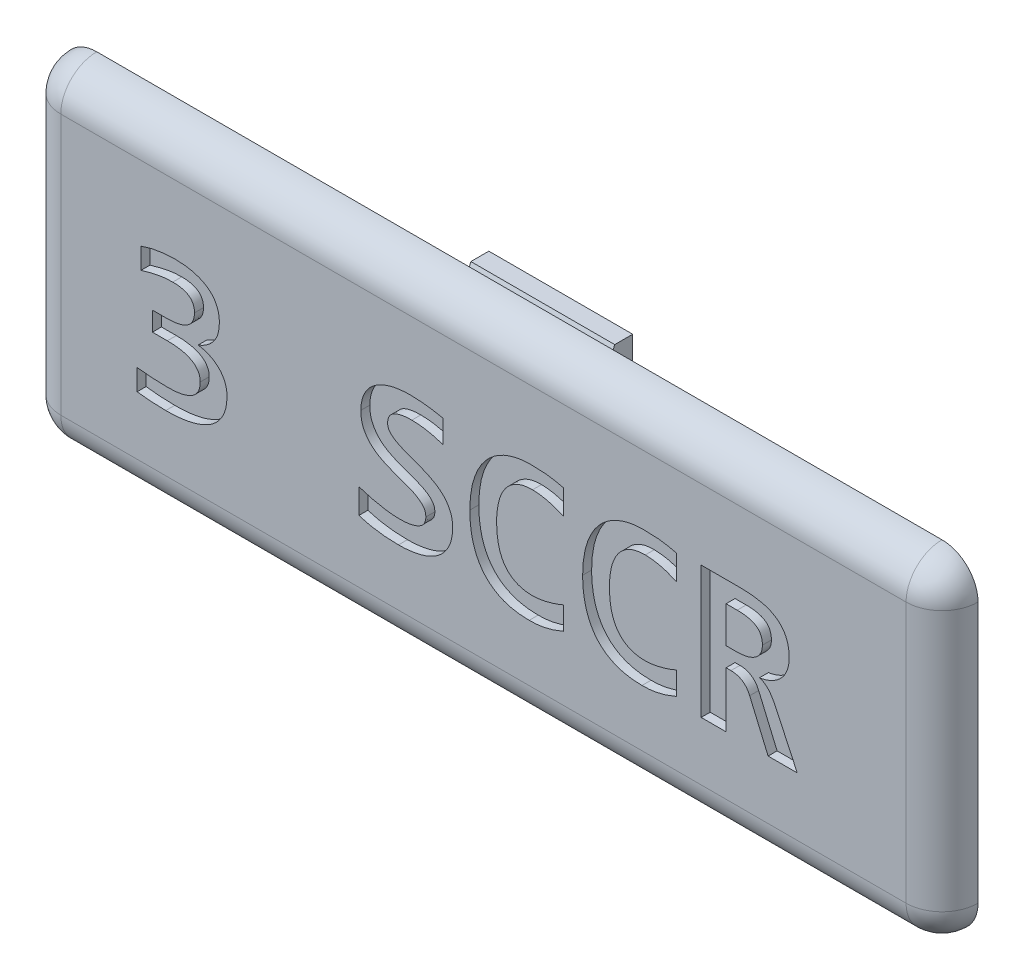
SolidWorks part; units mm, degrees
ref_plane "Front Plane" through (0, 0, 0) normal (0, 0, 1) x (1, 0, 0)
ref_plane "Top Plane" through (0, 0, 0) normal (0, 1, 0) x (1, 0, 0)
ref_plane "Right Plane" through (0, 0, 0) normal (1, 0, 0) x (0, 0, -1)
sketch "Sketch1" plane through (0, 0, 0) normal (0, 0, 1) x (1, 0, 0)
  line L13 (25.5, -7.25) -> (25.5, 7.25) construction
  line L14 (-23.5, -9.25) -> (-5, -9.25) construction
  line L15 (-25.5, 7.25) -> (-25.5, -7.25) construction
  line L16 (13, 9.25) -> (-23.5, 9.25) construction
  line L17 (25.5, -7.25) -> (25.5, 7.25)
  line L18 (-23.5, -9.25) -> (23.5, -9.25)
  line L19 (-25.5, 7.25) -> (-25.5, -7.25)
  line L20 (23.5, 9.25) -> (-23.5, 9.25)
  line L28 (23.75, -7.75) -> (23.75, 7.75)
  line L29 (-23.75, -7.5) -> (11.5, -7.5)
  line L30 (-23.75, 7.5) -> (-23.75, -7.5)
  line L31 (13, 7.5) -> (-23.75, 7.5)
  line L32 (-23.75, -7.5) -> (23.75, -7.5) construction
  line L33 (-23.75, 7.5) -> (-23.75, -7.5) construction
  line L34 (23.75, 7.5) -> (-23.75, 7.5) construction
  line L35 (23.75, -7.75) -> (23.75, 7.75) construction
  arc A0 (25.5, 7.25) -> (23.5, 9.25) centre (23.5, 7.25) ccw construction
  arc A1 (23.5, -9.25) -> (25.5, -7.25) centre (23.5, -7.25) ccw construction
  arc A2 (-25.5, -7.25) -> (-23.5, -9.25) centre (-23.5, -7.25) ccw construction
  arc A3 (-23.5, 9.25) -> (-25.5, 7.25) centre (-23.5, 7.25) ccw construction
  arc A4 (25.5, 7.25) -> (23.5, 9.25) centre (23.5, 7.25) ccw
  arc A5 (23.5, -9.25) -> (25.5, -7.25) centre (23.5, -7.25) ccw
  arc A6 (-25.5, -7.25) -> (-23.5, -9.25) centre (-23.5, -7.25) ccw
  arc A7 (-23.5, 9.25) -> (-25.5, 7.25) centre (-23.5, 7.25) ccw
  dimension "D1" = 0.25
  dimension "D2" = 0.25
extrude "Boss-Extrude1" add sketch "Sketch1" along normal blind 2
sketch "Sketch3" plane through (0, 0, 0) normal (0, 0, -1) x (-1, 0, 0)
  line L0 (-23.75, -7.75) -> (-23.75, 7.75) construction
  line L1 (-23.75, 7.5) -> (23.75, 7.5) construction
  line L2 (23.75, 7.5) -> (23.75, -7.5) construction
  line L3 (23.75, -7.5) -> (-23.75, -7.5) construction
  line L4 (-23.75, -7.5) -> (-23.75, 7.5)
  line L5 (-23.75, 7.5) -> (23.75, 7.5)
  line L6 (23.75, 7.5) -> (23.75, -7.5)
  line L7 (23.75, -7.5) -> (-23.75, -7.5)
extrude "Boss-Extrude2" add sketch "Sketch3" along normal blind 1
sketch "Sketch4" plane through (0, 0, -1) normal (0, 0, -1) x (-1, 0, 0)
  line L0 (-23.75, -7.5) -> (23.75, -7.5) construction
  line L1 (-8.75, -7.5) -> (-18.25, -7.5)
  line L2 (-8.75, -7.5) -> (-8.75, -2.5)
  line L3 (-8.75, -2.5) -> (-18.25, -2.5)
  line L4 (-18.25, -7.5) -> (-18.25, -2.5)
  line L5 (-11.5, -7.75) -> (-15.5, -7.75) construction
  point P4 (-13.5, -2.5)
  point P9 (-13.5, -7.75)
  dimension "D1" = 5
  dimension "D3" = 9.5
extrude "Cut-Extrude1" cut sketch "Sketch4" against normal blind 1
sketch "Sketch5" plane through (0, 0, -1) normal (0, 0, -1) x (-1, 0, 0)
  line L1 (-13, 7.75) -> (-21, 7.75)
  line L2 (-13, 7.75) -> (-13, -0.75)
  line L3 (-13, -0.75) -> (-21, -0.75)
  line L4 (-21, 7.75) -> (-21, -0.75)
  line L5 (-24, 7.75) -> (24, 7.75) construction
  dimension "D1" = 8
  dimension "D2" = 8.5
extrude "Cut-Extrude2" cut sketch "Sketch5" against normal blind 1
sketch "Sketch6" plane through (0, 0, 0) normal (0, 0, -1) x (-1, 0, 0)
  line L1 (-11.5, -9.25) -> (-15.5, -9.25)
  line L2 (-11.5, -9.25) -> (-11.5, -7.5)
  line L3 (-11.5, -7.5) -> (-15.5, -7.5)
  line L4 (-15.5, -9.25) -> (-15.5, -7.5)
  line L6 (23.75, -7.5) -> (-23.75, -7.5) construction
  line L8 (-11.5, -9.25) -> (-15.5, -9.25) construction
  line L9 (23.5, -9.25) -> (-23.5, -9.25) construction
  point P8 (-13.5, -7.5)
  point P11 (-13.5, -9.25)
  dimension "D1" = 4
extrude "Boss-Extrude3" add sketch "Sketch6" along normal blind 1.75
sketch "Sketch8" plane through (0, 0, 0) normal (1, 0, 0) x (0, 0, -1)
  line L1 (1, -7.5) -> (1, 7.5) construction
  line L2 (2.3, 6.05) -> (2.3, 8.25)
  line L3 (1, 5.25) -> (1, 7.5)
  line L4 (1, 7.5) -> (1.3, 8.25)
  line L5 (1.3, 8.25) -> (2.3, 8.25)
  line L6 (2.3, 6.05) -> (1, 5.25)
  dimension "D1" = 0.3
  dimension "D2" = 1
  dimension "D3" = 3
  dimension "D4" = 0.75
  dimension "D5" = 0.8
extrude "Boss-Extrude4" add sketch "Sketch8" against normal blind 4 and the other way blind 4
mirror "Mirror1" about plane through (0, 0, 0) normal (0, 1, 0) of "Boss-Extrude4"
fillet "Fillet1" radius 2 8 edges at (-24.9142, 8.6642, 2) (0, 9.25, 2) (24.9142, 8.6642, 2) (25.5, 0, 2) (24.9142, -8.6642, 2) (0, -9.25, 2) (-24.9142, -8.6642, 2) (-25.5, 0, 2)
sketch "Sketch9" plane through (0, 0, 2) normal (0, 0, 1) x (1, 0, 0)
  line L0 (-20, -4) -> (20, -4) construction
  line L1 (-23.75, -7.5) -> (23.75, -7.5) construction
  text T0 "<b>3 SCCR</b>" font "Consolas" height in points 28
  point P2 (0, -4)
  dimension "D1" = 40
  dimension "D2" = 3.5
extrude "Cut-Extrude3" cut sketch "Sketch9" against normal blind 0.5
